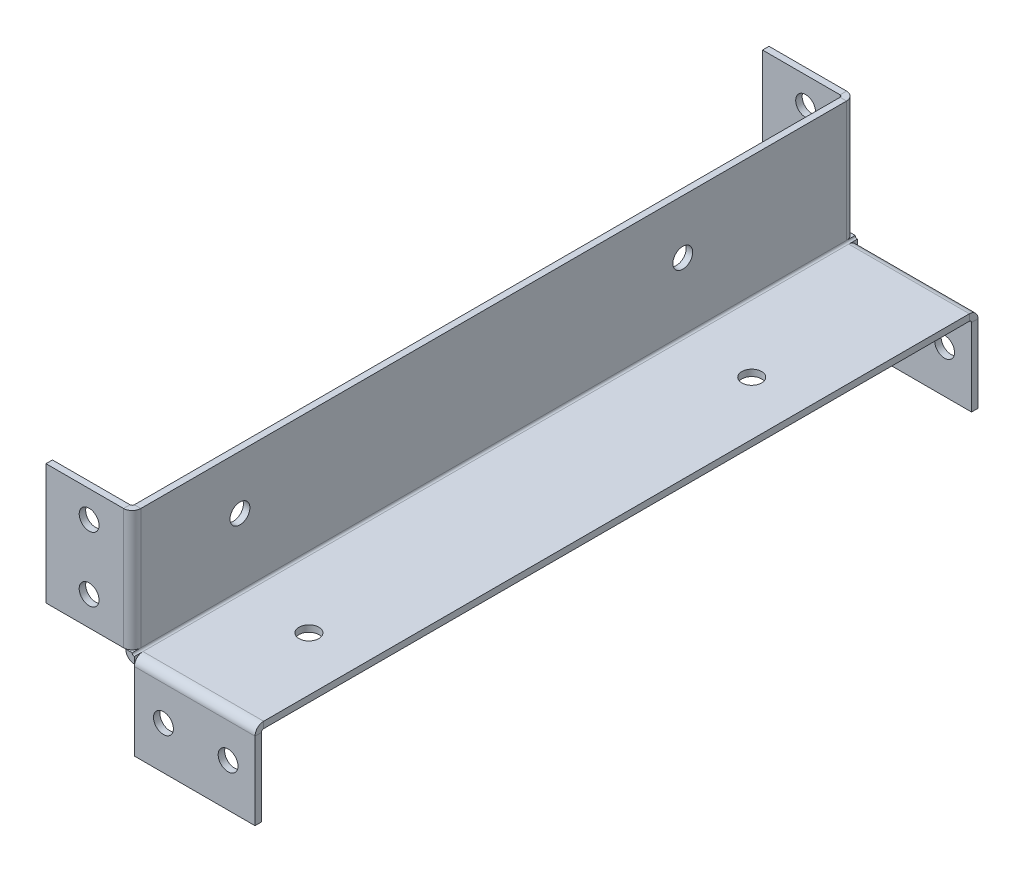
SolidWorks part; units mm, degrees
note: The reader was unsure of these and kept them because the rebuilt part matched: flange length of "Edge-Flange1", "Edge-Flange2".
ref_plane "Front Plane" through (0, 0, 0) normal (0, 0, 1) x (1, 0, 0)
ref_plane "Top Plane" through (0, 0, 0) normal (0, 1, 0) x (1, 0, 0)
ref_plane "Right Plane" through (0, 0, 0) normal (1, 0, 0) x (0, 0, -1)
sketch "Sketch1" plane through (0, 0, 0) normal (0, 1, 0) x (1, 0, 0)
  line L1 (30, 167.75) -> (-30, 167.75)
  line L2 (30, 167.75) -> (30, -167.75)
  line L3 (30, -167.75) -> (-30, -167.75)
  line L4 (-30, 167.75) -> (-30, -167.75)
  line L5 (30, 167.75) -> (-30, -167.75) construction
  line L6 (30, -167.75) -> (-30, 167.75) construction
  point P0 (0, 0)
  dimension "D1" = 60
  dimension "D2" = 335.5
sheet metal parameters "Sheet-Metal1" thickness 3 parameters "D1"=1
base flange "Base-Flange1" sketch "Sketch1" thickness 3 reverse thickness direction yes parameters "D1"=1
edge flange "Edge-Flange1" sketch "Sketch5" flange angle 90 flange length 60 flange position material inside bend radius 1 thickness 3 parameters "D6"=10
sketch "Sketch5" plane through (-30, 3, 0) normal (-1, 0, 0) x (0, 0, 1)
  line L2 (-167.75, 0) -> (-167.75, 57)
  line L3 (-167.75, 57) -> (167.75, 57)
  line L4 (167.75, 57) -> (167.75, 0)
  line L5 (-167.75, 0) -> (167.75, 0) construction
  line L6 (-167.75, 0) -> (167.75, 0)
bend "EdgeBend1" bend radius 1 bend angle 90 parameters "D5"=1
edge flange "Edge-Flange2" sketch "Sketch14" flange profiles "Sketch14", "Sketch15", "Sketch16", "Sketch17" flange angle 90 flange length 40 flange position material inside bend radius 1 thickness 3 relief none parameters "D6"=10, "D8"=0.5
sketch "Sketch14" plane through (-30, 0, 167.75) normal (0, 0, -1) x (0, -1, 0)
  line L1 (-4, 0) -> (-60, 0) construction
  line L2 (-60, 0) -> (-60, 37)
  line L3 (-60, 37) -> (-4, 37)
  line L4 (-4, 37) -> (-4, 0)
  line L5 (-4, 0) -> (-60, 0)
sketch "Sketch15" plane through (0, 0, 167.75) normal (0, 0, -1) x (1, 0, 0)
  line L0 (30, 0) -> (-26, 0) construction
  line L1 (30, 0) -> (-26, 0)
  line L2 (30, 0) -> (30, 37)
  line L3 (30, 37) -> (-26, 37)
  line L4 (-26, 37) -> (-26, 0)
sketch "Sketch16" plane through (-30, 0, -167.75) normal (0, 0, 1) x (0, 1, 0)
  line L0 (60, 0) -> (4, 0) construction
  line L1 (60, 0) -> (4, 0)
  line L2 (60, 0) -> (60, 37)
  line L3 (60, 37) -> (4, 37)
  line L4 (4, 37) -> (4, 0)
sketch "Sketch17" plane through (0, 0, -167.75) normal (0, 0, 1) x (-1, 0, 0)
  line L0 (26, 0) -> (-30, 0) construction
  line L1 (26, 0) -> (-30, 0)
  line L2 (26, 0) -> (26, 37)
  line L3 (26, 37) -> (-30, 37)
  line L4 (-30, 37) -> (-30, 0)
bend "EdgeBend2" bend radius 1 bend angle 90 parameters "D5"=2
bend "EdgeBend3" bend radius 1 bend angle 90 parameters "D5"=3
bend "EdgeBend4" bend radius 1 bend angle 90 parameters "D5"=4
bend "EdgeBend5" bend radius 1 bend angle 90 parameters "D5"=5
sketch "Sketch18" plane through (0, 0, 167.75) normal (0, 0, 1) x (1, 0, 0)
  line L0 (-26, 3) -> (30, 3) construction
  line L1 (-27, 60) -> (-27, 4) construction
  line L2 (-67, 60) -> (-31, 60) construction
  line L3 (30, -1) -> (30, -37) construction
  circle A0 centre (-47, 47.5) radius 4.6
  circle A1 centre (-47, 17.5) radius 4.6
  circle A2 centre (-12.5, -17) radius 4.6
  circle A3 centre (17.5, -17) radius 4.6
  dimension "D7" = 9.2
  dimension "D1" = 30
  dimension "D2" = 30
  dimension "D3" = 20
  dimension "D4" = 20
  dimension "D5" = 12.5
  dimension "D6" = 12.5
extrude "Extrude1" cut sketch "Sketch18" against normal through all normal cut yes
sketch "Sketch21" plane through (0, 0, 0) normal (0, -1, 0) x (1, 0, 0)
  line L0 (30, 163.75) -> (30, -163.75) construction
  line L1 (-26, -167.75) -> (30, -167.75) construction
  line L2 (0, 0) -> (113.8203, 0) construction
  line L3 (30, 167.75) -> (-26, 167.75) construction
  circle A0 centre (5, -87.75) radius 4.6
  circle A1 centre (5, 117.75) radius 4.6
  dimension "D2" = 9.2
  dimension "D6" = 9.2
  dimension "D1" = 25
  dimension "D3" = 80
  dimension "D4" = 25
  dimension "D5" = 50
extrude "Cut-Extrude1" cut sketch "Sketch21" against normal blind 10
sketch "Sketch22" plane through (-30, 0, 0) normal (-1, 0, 0) x (0, 0, 1)
  line L0 (-167.75, 60) -> (-167.75, 4) construction
  line L1 (163.75, 60) -> (-163.75, 60) construction
  line L2 (0, 0) -> (0, 85.4293) construction
  line L4 (167.75, 4) -> (167.75, 60) construction
  circle A0 centre (-87.75, 35) radius 4.6
  circle A1 centre (117.75, 35) radius 4.6
  dimension "D3" = 9.2
  dimension "D5" = 9.2
  dimension "D1" = 80
  dimension "D2" = 25
  dimension "D4" = 25
  dimension "D6" = 50
extrude "Cut-Extrude2" cut sketch "Sketch22" against normal blind 10 contours A0 | A1
flat pattern "Flat-Pattern1" [suppressed]
sketch "Bend-Lines1" plane through (0, 4, 0) normal (0, 1, 0) x (-1, 0, 0)
  line L0 (25, -126.4012) -> (-30, -126.4012) construction
  line L1 (82.8023, -126.4012) -> (27.8023, -126.4012) construction
  line L2 (-30, 126.4012) -> (25, 126.4012) construction
  line L3 (27.8023, 126.4012) -> (82.8023, 126.4012) construction
  line L4 (26.4012, -130) -> (26.4012, 130) construction
  line L5 (25, -126.4012) -> (-30, -126.4012) construction
  line L6 (82.8023, -126.4012) -> (27.8023, -126.4012) construction
  line L7 (-30, 126.4012) -> (25, 126.4012) construction
  line L8 (27.8023, 126.4012) -> (82.8023, 126.4012) construction
  line L9 (26.4012, -130) -> (26.4012, 130) construction
bend of the flat pattern "Flatten-<EdgeBend1>1"
bend of the flat pattern "Flatten-<EdgeBend2>1"
bend of the flat pattern "Flatten-<EdgeBend3>1"
bend of the flat pattern "Flatten-<EdgeBend4>1"
bend of the flat pattern "Flatten-<EdgeBend5>1"
